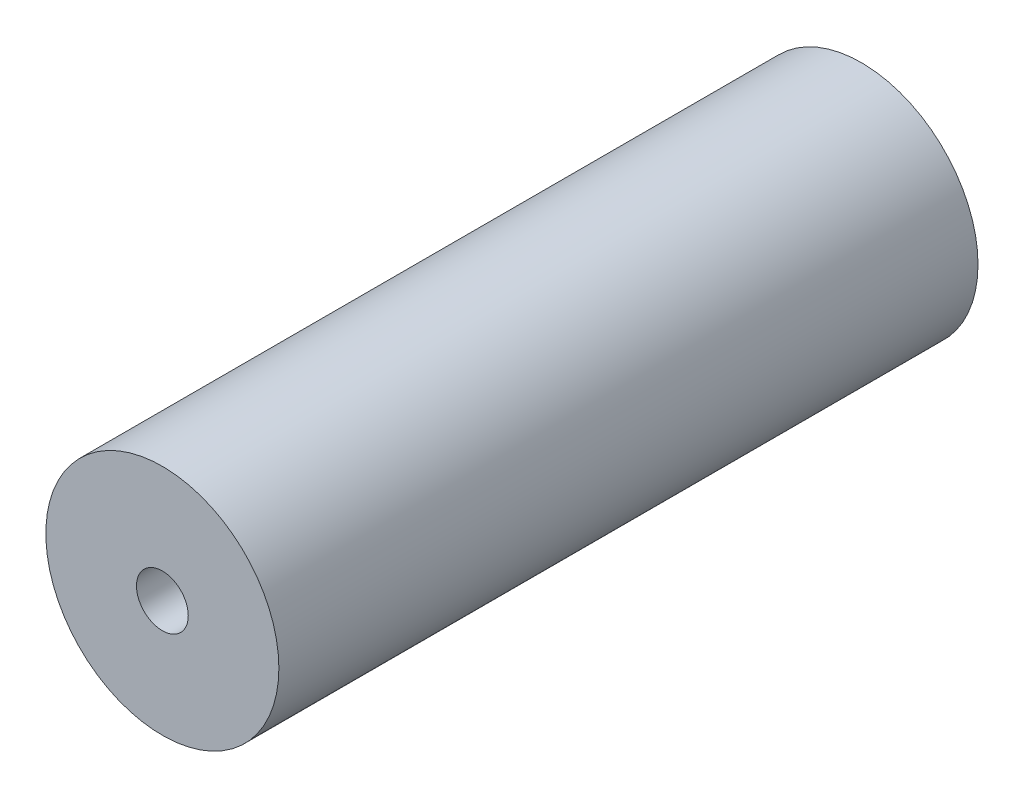
SolidWorks part; units mm, degrees
material "Cast Alloy Steel"
ref_plane "Front Plane" through (0, 0, 0) normal (0, 0, 1) x (1, 0, 0)
ref_plane "Top Plane" through (0, 0, 0) normal (0, 1, 0) x (1, 0, 0)
ref_plane "Right Plane" through (0, 0, 0) normal (1, 0, 0) x (0, 0, -1)
sketch "Sketch2" plane through (0, 0, 0) normal (0, 0, 1) x (1, 0, 0)
  circle A0 centre (0, 0) radius 18
extrude "Boss-Extrude1" add sketch "Sketch2" along normal blind 54 and the other way blind 54
sketch "Sketch3" plane through (0, 0, 54) normal (0, 0, 1) x (1, 0, 0)
  circle A0 centre (0, 0) radius 4
  dimension "D1" = 0
extrude "Cut-Extrude1" cut sketch "Sketch3" against normal blind 122
sketch "Sketch4" plane through (0, 0, -54) normal (0, 0, -1) x (-1, 0, 0)
  line L0 (0, 35.8542) -> (0, -31.7202) construction
  line L1 (-38.0006, 0) -> (55.6495, 0) construction
  circle A0 centre (0, 0) radius 14 construction
  circle A1 centre (0, 14) radius 1.5
  circle A2 centre (14, 0) radius 1.5
  circle A3 centre (0, -14) radius 1.5
  circle A4 centre (-14, 0) radius 1.5
extrude "Cut-Extrude2" cut sketch "Sketch4" against normal blind 5
